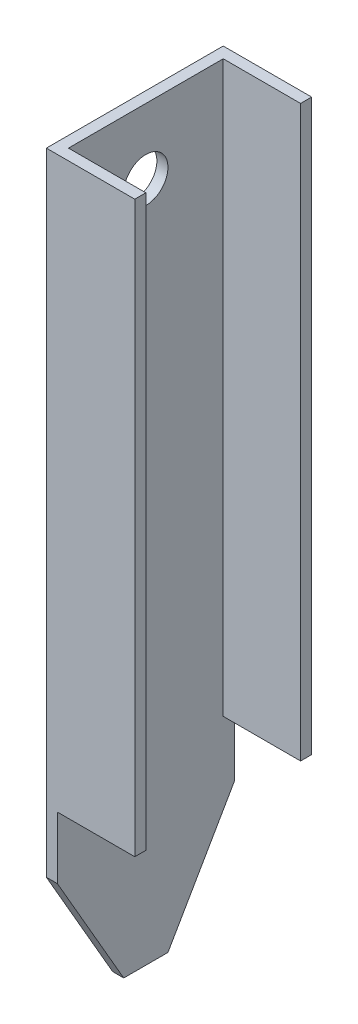
SolidWorks part; units mm, degrees
ref_plane "Front Plane" through (0, 0, 0) normal (0, 0, 1) x (1, 0, 0)
ref_plane "Top Plane" through (0, 0, 0) normal (0, 1, 0) x (1, 0, 0)
ref_plane "Right Plane" through (0, 0, 0) normal (1, 0, 0) x (0, 0, -1)
sketch "Sketch1" plane through (0, 0, 0) normal (0, 1, 0) x (1, 0, 0)
  line L0 (-20.955, 0) -> (-20.955, 25.4)
  line L1 (-20.955, 25.4) -> (4.445, 25.4)
  line L2 (4.445, 25.4) -> (4.445, 22.225)
  line L3 (4.445, 22.225) -> (-17.78, 22.225)
  line L4 (-17.78, 22.225) -> (-17.78, -22.225)
  line L5 (-17.78, -22.225) -> (4.445, -22.225)
  line L6 (4.445, -22.225) -> (4.445, -25.4)
  line L7 (4.445, -25.4) -> (-20.955, -25.4)
  line L8 (-20.955, -25.4) -> (-20.955, 0)
  dimension "D1" = 3.175
  dimension "D2" = 3.175
  dimension "D3" = 3.175
  dimension "D4" = 25.4
  dimension "D5" = 25.4
  dimension "D6" = 25.4
  dimension "D7" = 25.4
extrude "Boss-Extrude1" add sketch "Sketch1" along normal mid plane 214.376
sketch "Sketch2" plane through (0, 0, 25.4) normal (0, 0, 1) x (1, 0, 0)
  line L0 (-17.78, -107.188) -> (-17.78, -56.388)
  line L1 (-20.955, -107.188) -> (4.445, -107.188) construction
  line L2 (-17.78, -56.388) -> (4.445, -56.388)
  line L3 (4.445, 107.188) -> (4.445, -107.188) construction
  line L4 (4.445, -56.388) -> (4.445, -107.188)
  line L5 (4.445, -107.188) -> (-17.78, -107.188)
  line L6 (-20.955, 107.188) -> (-20.955, -107.188) construction
  dimension "D1" = 3.175
  dimension "D2" = 22.225
  dimension "D3" = 50.8
extrude "Cut-Extrude1" cut sketch "Sketch2" against normal blind 208.026
sketch "Sketch3" plane through (-20.955, 0, 0) normal (-1, 0, 0) x (0, 0, 1)
  line L1 (-25.4, -107.188) -> (25.4, -107.188) construction
  circle A0 centre (0, 88.138) radius 6.35
  dimension "D1" = 12.7
  dimension "D2" = 195.326
extrude "Cut-Extrude2" cut sketch "Sketch3" against normal blind 45.974
chamfer "Chamfer1" distance 19.05 angle 60 1 edges at (-19.3675, -107.188, -25.4) first distance on face at (-19.3675, -107.188, 0)
chamfer "Chamfer2" distance 19.05 angle 60 1 edges at (-19.3675, -107.188, 25.4) first distance on face at (-19.3675, -107.188, 9.525)
